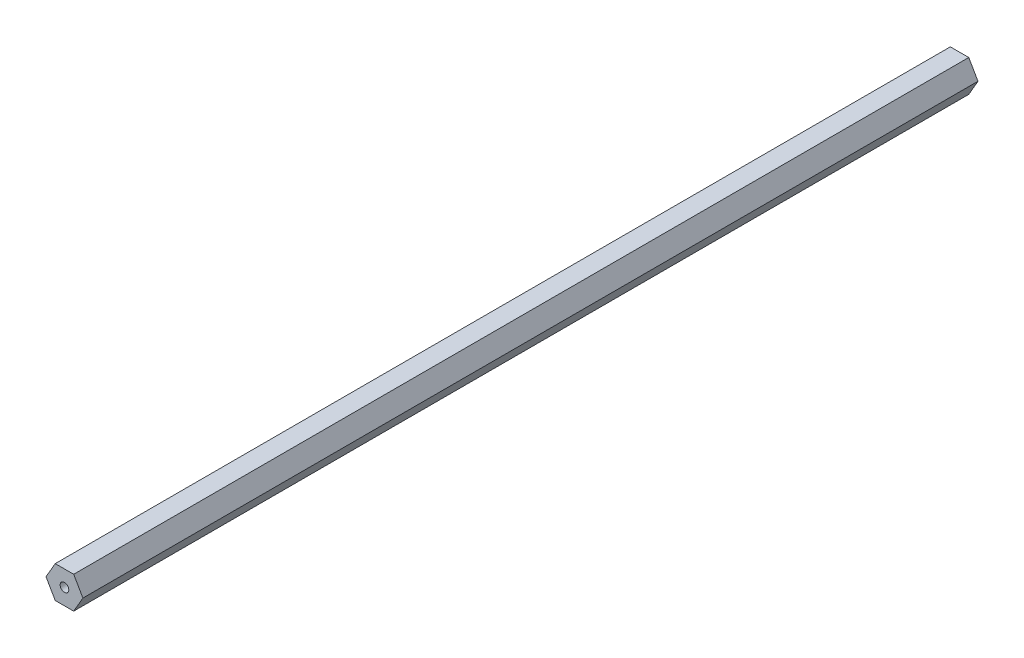
SolidWorks part; units mm, degrees
material "7075-T6 (SN)"
ref_plane "Front Plane" through (0, 0, 0) normal (0, 0, 1) x (1, 0, 0)
ref_plane "Top Plane" through (0, 0, 0) normal (0, 1, 0) x (1, 0, 0)
ref_plane "Right Plane" through (0, 0, 0) normal (1, 0, 0) x (0, 0, -1)
other "Configuration Table"
sketch "Sketch1" plane through (0, 0, 0) normal (0, 0, 1) x (1, 0, 0)
  line L1 (7.3323, 0) -> (3.6662, 6.35)
  line L2 (3.6662, 6.35) -> (-3.6662, 6.35)
  line L3 (-3.6662, 6.35) -> (-7.3323, 0)
  line L4 (-7.3323, 0) -> (-3.6662, -6.35)
  line L5 (-3.6662, -6.35) -> (3.6662, -6.35)
  line L6 (3.6662, -6.35) -> (7.3323, 0)
  circle A0 centre (0, 0) radius 6.35 construction
  circle A1 centre (0, 0) radius 1.7145
  dimension "D2" = 3.429
  dimension "D1" = 12.7
extrude "Boss-Extrude1" add sketch "Sketch1" along normal mid plane 355.6
fillet "Fillet1" [suppressed] radius 0.635
equation "\"length\"= 14"
equation "\"D1@Boss-Extrude1\"=\"length\""
